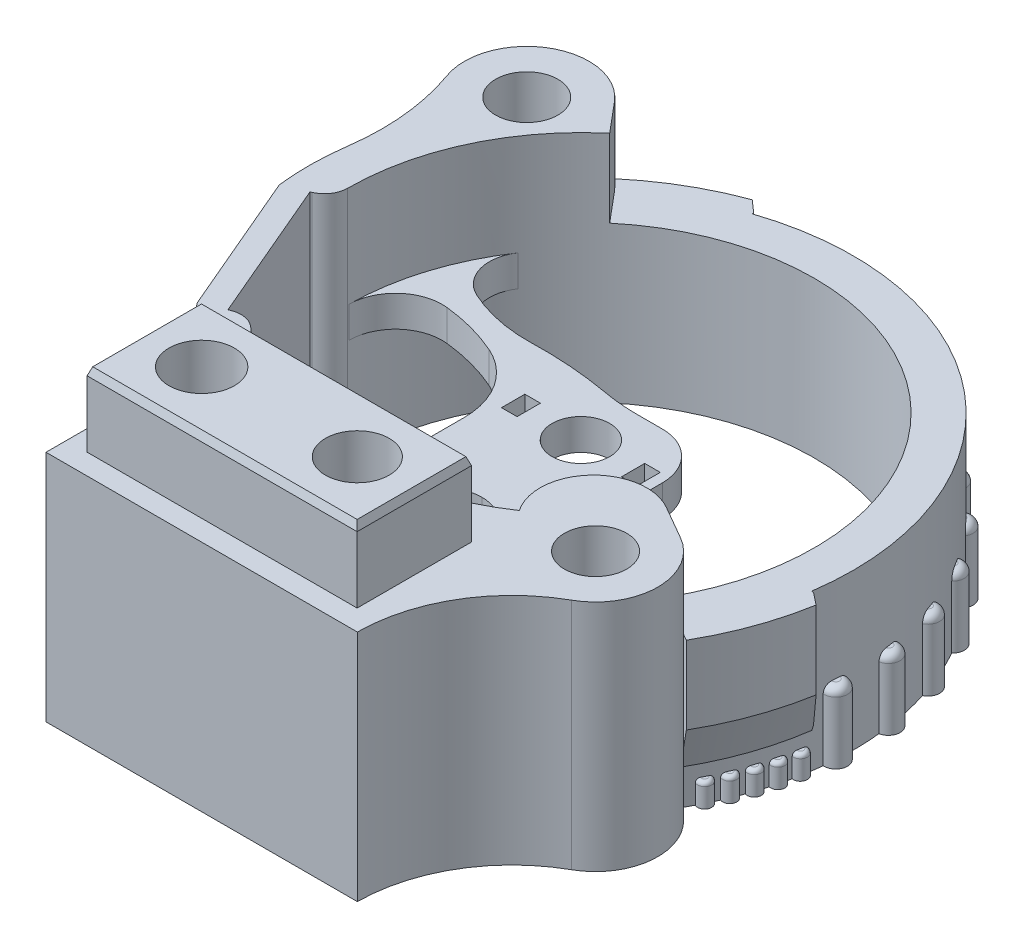
SolidWorks part; units mm, degrees
ref_plane "Спереди" through (0, 0, 0) normal (0, 0, 1) x (1, 0, 0)
ref_plane "Сверху" through (0, 0, 0) normal (0, 1, 0) x (1, 0, 0)
ref_plane "Справа" through (0, 0, 0) normal (1, 0, 0) x (0, 0, -1)
sketch "Sketch1" plane through (0, 0, 0) normal (0, 1, 0) x (1, 0, 0)
  circle A0 centre (0, 0) radius 35
  dimension "D1" = 70
extrude "Boss-Extrude1" add sketch "Sketch1" along normal blind 30
sketch "Sketch6" plane through (0, 30, 0) normal (0, 1, 0) x (1, 0, 0)
  circle A0 centre (0, 0) radius 30
  circle A1 centre (0, 0) radius 35 construction
  dimension "D1" = 5
  dimension "D2" = 60
extrude "Cut-Extrude3" cut sketch "Sketch6" against normal through all
sketch "Sketch7" plane through (0, 30, 0) normal (0, 1, 0) x (1, 0, 0)
  line L0 (0, 0) -> (-22.4976, 26.8116) construction
  line L1 (0, 0) -> (30.3109, -17.5) construction
  line L2 (0, 0) -> (0, -30) construction
  line L3 (0, 0) -> (0, 30) construction
  line L4 (-19.2836, 22.9813) -> (-22.4976, 26.8116)
  line L5 (25.9808, -15) -> (30.3109, -17.5)
  circle A0 centre (0, 0) radius 35 construction
  circle A1 centre (0, 0) radius 30 construction
  arc A2 (-19.2836, 22.9813) -> (25.9808, -15) centre (0, 0) cw
  arc A3 (-22.4976, 26.8116) -> (30.3109, -17.5) centre (0, 0) cw
  dimension "D1" = 40
  dimension "D2" = 60
extrude "Cut-Extrude4" cut sketch "Sketch7" against normal blind 10
sketch "Sketch8" plane through (0, 20, 0) normal (0, 1, 0) x (1, 0, 0)
  line L0 (0, 0) -> (0, -38.8668) construction
  line L3 (10, -33.541) -> (10, 6.459)
  line L4 (10, 6.459) -> (-10, 6.459)
  line L5 (-10, -33.541) -> (-10, 6.459)
  line L6 (10, -33.541) -> (-10, 6.459) construction
  line L7 (10, 6.459) -> (-10, -33.541) construction
  arc A0 (-10, -33.541) -> (10, -33.541) centre (0, 0) ccw
  arc A3 (-22.4976, 26.8116) -> (30.3109, -17.5) centre (0, 0) ccw construction
  point P3 (0, -13.541)
  dimension "D1" = 40
  dimension "D2" = 20
extrude "Boss-Extrude3" add sketch "Sketch8" along normal blind 4 from offset 7 offset against normal yes
sketch "Sketch9" plane through (0, 0, 0) normal (0, -1, 0) x (1, 0, 0)
  line L0 (0, -35) -> (0, 35) construction
  line L2 (-20, 28.7228) -> (20, 28.7228)
  line L3 (-20, 28.7228) -> (-20, 48.7228)
  line L4 (-20, 48.7228) -> (20, 48.7228)
  line L5 (20, 28.7228) -> (20, 48.7228)
  line L6 (-20, 28.7228) -> (20, 48.7228) construction
  line L7 (-20, 48.7228) -> (20, 28.7228) construction
  circle A0 centre (0, 0) radius 35 construction
  point P5 (0, 38.7228)
  dimension "D1" = 40
  dimension "D2" = 20
extrude "Boss-Extrude4" add sketch "Sketch9" against normal up to surface (30 mm away)
sketch "Sketch10" plane through (0, 17, 0) normal (0, 1, 0) x (1, 0, 0)
  line L0 (3.7, 0) -> (10, 0) construction
  line L1 (-3.7, 0) -> (-10, 0) construction
  line L2 (8.7, -1.5) -> (6.7, -1.5)
  line L3 (8.7, -1.5) -> (8.7, 1.5)
  line L4 (8.7, 1.5) -> (6.7, 1.5)
  line L5 (6.7, -1.5) -> (6.7, 1.5)
  line L6 (8.7, -1.5) -> (6.7, 1.5) construction
  line L7 (8.7, 1.5) -> (6.7, -1.5) construction
  line L9 (-6.7, -1.5) -> (-8.7, -1.5)
  line L10 (-6.7, -1.5) -> (-6.7, 1.5)
  line L11 (-6.7, 1.5) -> (-8.7, 1.5)
  line L12 (-8.7, -1.5) -> (-8.7, 1.5)
  line L13 (-6.7, -1.5) -> (-8.7, 1.5) construction
  line L14 (-6.7, 1.5) -> (-8.7, -1.5) construction
  circle A0 centre (0, 0) radius 10 construction
  circle A1 centre (0, 0) radius 3.7
  point P6 (7.7, 0)
  point P13 (-7.7, 0)
  dimension "D1" = 20
  dimension "D2" = 7.4
  dimension "D3" = 4
  dimension "D4" = 3
  dimension "D5" = 2
  dimension "D6" = 4
extrude "Cut-Extrude5" cut sketch "Sketch10" against normal through all
sketch "Sketch11" plane through (0, 30, 0) normal (0, 1, 0) x (1, 0, 0)
  line L0 (-20, -38.7228) -> (20, -38.7228) construction
  line L1 (-20, -48.7228) -> (-20, -28.7228) construction
  line L2 (20, -28.7228) -> (20, -48.7228) construction
  circle A0 centre (-10, -38.7228) radius 4.2
  circle A1 centre (10, -38.7228) radius 4.2
  point P10 (0, -38.7228)
  dimension "D1" = 8.4
  dimension "D2" = 20
  dimension "D3" = 10
extrude "Cut-Extrude6" cut sketch "Sketch11" against normal through all
sketch "Sketch15" plane through (0, 30, 0) normal (0, 1, 0) x (1, 0, 0)
  line L0 (19.9782, -38.7228) -> (-20.0306, -38.7228) construction
  line L4 (17.3238, -46.0728) -> (-17.3762, -46.0728)
  line L5 (17.3238, -46.0728) -> (17.3238, -31.3728)
  line L6 (17.3238, -31.3728) -> (-17.3762, -31.3728)
  line L7 (-17.3762, -46.0728) -> (-17.3762, -31.3728)
  line L8 (17.3238, -46.0728) -> (-17.3762, -31.3728) construction
  line L9 (17.3238, -31.3728) -> (-17.3762, -46.0728) construction
  circle A0 centre (-10, -38.7228) radius 4.2
  circle A1 centre (10, -38.7228) radius 4.1
  circle A4 centre (-10, -38.7228) radius 4.2 construction
  point P6 (-0.0262, -38.7228)
  dimension "D1" = 14.7
  dimension "D2" = 34.7
extrude "Boss-Extrude6" add sketch "Sketch15" along normal blind 9.5
chamfer "Chamfer3" distance 1 angle 20 4 edges at (17.3238, 39.5, 38.7228) (-0.0262, 39.5, 46.0728) (-17.3762, 39.5, 38.7228) (-0.0262, 39.5, 31.3728)
sketch "Sketch16" plane through (0, 0, 0) normal (0, -1, 0) x (1, 0, 0)
  line L0 (-20, 38.7228) -> (20, 38.7228) construction
  line L1 (-20, 48.7228) -> (-20, 28.7228) construction
  line L2 (20, 28.7228) -> (20, 48.7228) construction
  line L4 (-17.5, 46.2228) -> (17.5, 46.2228)
  line L5 (-17.5, 46.2228) -> (-17.5, 31.2228)
  line L6 (-17.5, 31.2228) -> (17.5, 31.2228)
  line L7 (17.5, 46.2228) -> (17.5, 31.2228)
  line L8 (-17.5, 46.2228) -> (17.5, 31.2228) construction
  line L9 (-17.5, 31.2228) -> (17.5, 46.2228) construction
  point P6 (0, 38.7228)
  dimension "D1" = 15
  dimension "D2" = 35
extrude "Cut-Extrude8" cut sketch "Sketch16" against normal blind 10
chamfer "Chamfer4" distance 1 angle 70 4 edges at (17.5, 0, 38.7228) (0, 0, 46.2228) (-17.5, 0, 38.7228) (0, 0, 31.2228)
sketch "Sketch18" plane through (0, 30, 0) normal (0, 1, 0) x (1, 0, 0)
  line L0 (-31.9117, 14.3752) -> (-22.4976, 26.8116) construction
  line L1 (-22.4976, 26.8116) -> (-19.2836, 22.9813) construction
  line L2 (-31.9117, 14.3752) -> (-27.3529, 12.3216)
  line L3 (-27.3529, 12.3216) -> (-19.2836, 22.9813) construction
  line L4 (-19.2836, 22.9813) -> (-22.4976, 26.8116)
  line L5 (25.9808, -15) -> (30.3109, -17.5) construction
  line L6 (19.6982, -28.9306) -> (16.8841, -24.7977)
  line L7 (25.9808, -15) -> (30.3109, -17.5)
  arc A0 (-22.4976, 26.8116) -> (-31.9117, 14.3752) centre (-28.6259, 21.6693) ccw
  arc A1 (-22.4976, 26.8116) -> (-20, -28.7228) centre (0, 0) ccw construction
  circle A2 centre (-28.6259, 21.6693) radius 4
  arc A3 (-19.2836, 22.9813) -> (-8.6603, -28.7228) centre (0, 0) ccw construction
  arc A4 (-27.3529, 12.3216) -> (-19.2836, 22.9813) centre (-24.5365, 18.5736) ccw
  arc A5 (30.3109, -17.5) -> (19.6982, -28.9306) centre (26.3109, -24.4282) cw
  arc A6 (20, -28.7228) -> (30.3109, -17.5) centre (0, 0) ccw construction
  circle A7 centre (26.3109, -24.4282) radius 4
  arc A8 (25.9808, -15) -> (16.8841, -24.7977) centre (22.5522, -20.9385) ccw
  dimension "D1" = 8
  dimension "D2" = 8
extrude "Boss-Extrude7" add sketch "Sketch18" against normal up to surface (30 mm away)
sketch "Sketch19" plane through (0, 30, 0) normal (0, 1, 0) x (1, 0, 0)
  circle A0 centre (-28.6259, 21.6693) radius 4
  arc A2 (-25.4189, 24.0599) -> (-30.0563, 17.9337) centre (-28.6259, 21.6693) ccw construction
  circle A3 centre (26.3109, -24.4282) radius 4
  arc A5 (22.8805, -26.4855) -> (28.1083, -20.8548) centre (26.3109, -24.4282) ccw construction
extrude "Cut-Extrude9" cut sketch "Sketch19" against normal through all
chamfer "Chamfer5" distance 10 angle 50 1 edges at (0, 13, 28.7228)
fillet "Fillet1" radius 20 1 edges at (0, 13, 16.8053)
sketch "Sketch20" plane through (0, 17, 0) normal (0, 1, 0) x (1, 0, 0)
  line L0 (0, -28.7228) -> (0, -3.7) construction
  line L1 (8.6603, -28.7228) -> (-8.6603, -28.7228) construction
  line L3 (5, -12.7228) -> (-5, -12.7228)
  line L4 (5, -12.7228) -> (5, -28.7228)
  line L5 (5, -28.7228) -> (-5, -28.7228)
  line L6 (-5, -12.7228) -> (-5, -28.7228)
  line L7 (5, -12.7228) -> (-5, -28.7228) construction
  line L8 (5, -28.7228) -> (-5, -12.7228) construction
  circle A0 centre (0, 0) radius 3.7 construction
  point P7 (0, -20.7228)
  dimension "D1" = 10
  dimension "D2" = 16
extrude "Cut-Extrude10" cut sketch "Sketch20" against normal through all
fillet "Fillet3" radius 6 2 edges at (10, 10.184, 28.2843) (-10, 10.184, 28.2843)
fillet "Fillet4" radius 6 2 edges at (10, 15, -6.459) (-10, 15, -6.459)
fillet "Fillet5" radius 5 2 edges at (-5, 14.8714, 12.7228) (5, 14.8714, 12.7228)
sketch "Sketch21" plane through (0, 0, 0) normal (0, -1, 0) x (1, 0, 0)
  circle A0 centre (34.9319, 2.1818) radius 1.5
  arc A1 (-22.4976, -26.8116) -> (30.3109, 17.5) centre (0, 0) ccw construction
  circle A2 centre (34.5618, -4.9512) radius 1.5
  circle A3 centre (32.7339, -11.8559) radius 1.5
  circle A4 centre (29.5261, -18.2377) radius 1.5
  circle A5 centre (25.0754, -23.8242) radius 1.5
  circle A6 centre (19.5717, -28.3768) radius 1.5
  circle A7 centre (13.2499, -31.7013) radius 1.5
  circle A8 centre (6.3799, -33.6559) radius 1.5
  circle A9 centre (-0.7451, -34.157) radius 1.5
  circle A10 centre (-7.821, -33.1833) radius 1.5
  point P26 (0.4047, 0.3972)
  dimension "D1" = 3
  dimension "D2" = 16
  dimension "D4" = 16
  dimension "D3" = 10
extrude "Boss-Extrude8" add sketch "Sketch21" against normal blind 9
fillet "Fillet6" radius 1 10 edges at (36.429, 9, 2.2753) (36.0467, 9, -5.1639) (34.1442, 9, -12.3668) (30.8023, 9, -19.026) (26.1628, 9, -24.8573) (20.4233, 9, -29.6116) (13.8284, 9, -33.0853) (6.6593, 9, -35.1296) (-0.7778, 9, -35.6566) (-8.1651, 9, -34.6433)
sketch "Sketch23" plane through (0, 20, 0) normal (0, 1, 0) x (1, 0, 0)
  line L0 (-23.977, 28.1798) -> (-22.4976, 26.8116)
  line L1 (-22.4976, 26.8116) -> (-11.1532, 33.1754)
  line L2 (-11.1532, 33.1754) -> (-11.7905, 35.0711)
  line L3 (-11.7905, 35.0711) -> (0, 0) construction
  line L4 (0, 0) -> (36.6227, -5.2703) construction
  line L5 (0, 0) -> (32.0429, -18.5) construction
  line L6 (36.6227, -5.2703) -> (34.6431, -4.9854)
  line L7 (34.6431, -4.9854) -> (30.3109, -17.5)
  line L8 (30.3109, -17.5) -> (32.0429, -18.5)
  line L9 (25.9808, -15) -> (30.3109, -17.5) construction
  circle A0 centre (0, 0) radius 37 construction
  arc A1 (30.3109, -17.5) -> (-22.4976, 26.8116) centre (0, 0) ccw construction
  arc A2 (-23.977, 28.1798) -> (-11.7905, 35.0711) centre (0, 0) cw
  arc A3 (-22.4976, 26.8116) -> (-31.9117, 14.3752) centre (-28.6259, 21.6693) ccw construction
  arc A4 (32.0429, -18.5) -> (36.6227, -5.2703) centre (0, 0) ccw
  dimension "D1" = 2
  dimension "D2" = 14
  dimension "D3" = 14
extrude "Boss-Extrude9" add sketch "Sketch23" against normal blind 10
chamfer "Chamfer6" distance 1 angle 60 2 edges at (-11.7905, 15, -35.0711) (36.6227, 15, 5.2703)
chamfer "Chamfer7" distance 2 angle 70 2 edges at (-17.1236, 10, -30.5251) (33.0743, 10, 11.4495)
sketch "Sketch24" plane through (0, 0, 0) normal (0, -1, 0) x (1, 0, 0)
  circle A0 centre (-12.1188, -32.835) radius 0.9
  arc A1 (-22.4976, -26.8116) -> (-9.2021, -33.7686) centre (0, 0) ccw construction
  circle A2 centre (-14.3797, -31.9096) radius 0.9
  circle A3 centre (-16.5706, -30.8288) radius 0.9
  circle A4 centre (-18.6808, -29.5978) radius 0.9
  circle A5 centre (-20.6999, -28.2226) radius 0.9
  circle A6 centre (34.4405, 6.233) radius 0.9
  arc A7 (34.8064, 3.6766) -> (30.3109, 17.5) centre (0, 0) ccw construction
  circle A8 centre (33.9218, 8.6202) radius 0.9
  circle A9 centre (33.2379, 10.9655) radius 0.9
  circle A10 centre (32.392, 13.2573) radius 0.9
  circle A11 centre (31.3883, 15.4846) radius 0.9
  point P13 (0, 0)
  point P17 (0, 0)
  point P32 (0, 0)
  dimension "D1" = 1.8
  dimension "D2" = 12
  dimension "D4" = 12
  dimension "D3" = 5
  dimension "D5" = 5
extrude "Boss-Extrude10" add sketch "Sketch24" against normal blind 3
fillet "Fillet10" radius 20 1 edges at (20, 15, 29.3448)
fillet "Fillet11" radius 30 1 edges at (-20, 15, 28.7228)
fillet "Fillet12" radius 30 1 edges at (-31.9117, 15, -14.3752)
sketch "Sketch25" plane through (0, 17, 0) normal (0, 1, 0) x (1, 0, 0)
  line L1 (4, 6.459) -> (-4, 6.459) construction
  line L3 (-34.6746, 4.7614) -> (-10, 0.459) construction
  arc A1 (-34.6746, 4.7614) -> (-10, 0.459) centre (-26.054, -18.7053) cw
  arc A2 (0, 6.459) -> (-19.0692, 14.435) centre (1.333, 36.4294) cw
  arc A3 (-27.3529, 12.3216) -> (-19.2836, 22.9813) centre (-24.5365, 18.5736) ccw construction
  arc A4 (-34.6746, 4.7614) -> (-19.0692, 14.435) centre (-22.8002, 3.0297) cw
  arc A5 (-10, 0.459) -> (0, 6.459) centre (4.8429, -12.9458) cw
  point P16 (-19.0692, 14.435)
  dimension "D1" = 30
  dimension "D2" = 25
  dimension "D3" = 12
  dimension "D4" = 20
extrude "Boss-Extrude11" add sketch "Sketch25" against normal up to surface (4 mm away) up to face at (7.7, 13, 0)
fillet "Fillet13" radius 6 1 edges at (-29.379, 15, -6.0726)
fillet "Fillet14" radius 10 1 edges at (-19.0692, 15, -14.435)
fillet "Fillet15" radius 10 1 edges at (-10, 15, -0.459)
sketch "Sketch28" plane through (0, 0, 0) normal (0, -1, 0) x (1, 0, 0)
  line L0 (-19.2836, -22.9813) -> (5.2094, -29.5442)
  arc A0 (-19.2836, -22.9813) -> (-27.3529, -12.3216) centre (0, 0) cw
  arc A1 (-19.2836, -22.9813) -> (-27.3529, -12.3216) centre (-24.5365, -18.5736) ccw construction
  arc A2 (-19.2836, -22.9813) -> (25.9808, 15) centre (0, 0) ccw construction
  arc A3 (-27.3529, -12.3216) -> (5.2094, -29.5442) centre (-14.531, -27.4733) cw
extrude "Cut-Extrude12" cut sketch "Sketch28" against normal through all
fillet "Fillet18" radius 5 1 edges at (-27.3529, 15, -12.3216)
fillet "Fillet19" radius 25 1 edges at (0, 15, -6.459)
sketch "Sketch29" plane through (0, 0, 0) normal (0, -1, 0) x (1, 0, 0)
  line L0 (-26.9231, 22.364) -> (-34.7742, 3.9694)
  line L1 (-26.9231, 22.364) -> (-22.0883, 20.3004) construction
  line L2 (-22.0883, 20.3004) -> (-29.9394, 1.9059) construction
  line L3 (-29.9394, 1.9059) -> (-34.7742, 3.9694) construction
  line L4 (-24.1639, 21.1863) -> (-32.015, 2.7918)
  line L5 (-32.015, 2.7918) -> (-29.9394, 1.9059)
  line L6 (-29.9394, 1.9059) -> (-22.0883, 20.3004)
  line L7 (-22.0883, 20.3004) -> (-24.1639, 21.1863)
  arc A2 (-26.9231, 22.364) -> (-34.6746, -4.7614) centre (0, 0) ccw construction
  arc A3 (-26.9231, 22.364) -> (-34.7742, 3.9694) centre (-30.8486, 13.1667) ccw
  arc A4 (-8.6603, 28.7228) -> (25.9808, 15) centre (0, 0) ccw construction
  dimension "D1" = 20
  dimension "D2" = 3
extrude "Cut-Extrude13" cut sketch "Sketch29" against normal through all
fillet "Fillet20" radius 3 2 edges at (-29.9394, 15, 1.9059) (-22.0883, 15, 20.3004)
fillet "Fillet21" radius 0.5 10 edges at (35.3261, 3, 6.3932) (34.7941, 3, 8.8419) (34.0926, 3, 11.2475) (33.225, 3, 13.5983) (32.1955, 3, 15.8828) (-21.2322, 3, -28.9483) (-19.1611, 3, -30.3589) (-16.9967, 3, -31.6215) (-14.7495, 3, -32.7301) (-12.4304, 3, -33.6793)
fillet "Fillet23" radius 50 1 edges at (-9.2224, 15, -8.3476)
